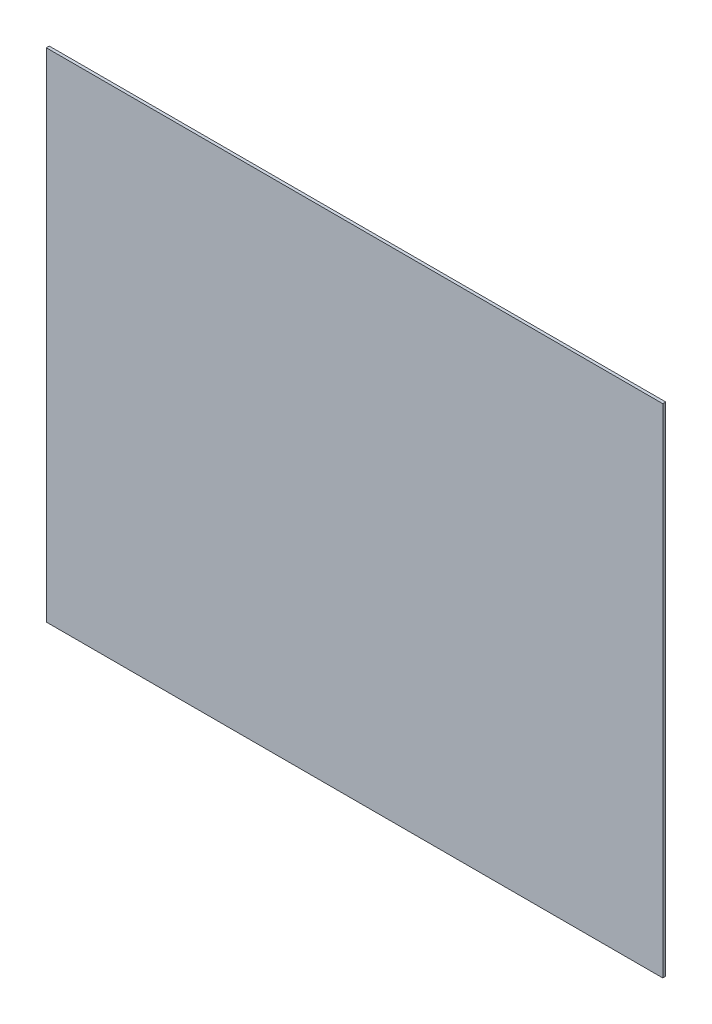
SolidWorks part; units mm, degrees
ref_plane "Front Plane" through (0, 0, 0) normal (0, 0, 1) x (1, 0, 0)
ref_plane "Top Plane" through (0, 0, 0) normal (0, 1, 0) x (1, 0, 0)
ref_plane "Right Plane" through (0, 0, 0) normal (1, 0, 0) x (0, 0, -1)
sketch "Sketch1" plane through (0, 0, 0) normal (0, 0, 1) x (1, 0, 0)
  line L1 (-581.6, -469.2) -> (581.6, -469.2)
  line L2 (-581.6, -469.2) -> (-581.6, 469.2)
  line L3 (-581.6, 469.2) -> (581.6, 469.2)
  line L4 (581.6, -469.2) -> (581.6, 469.2)
  line L5 (-581.6, -469.2) -> (581.6, 469.2) construction
  line L6 (-581.6, 469.2) -> (581.6, -469.2) construction
  line L7 (-581.6, -457.2) -> (-581.6, 457.2) construction
  line L8 (-609.6, 469.2) -> (609.6, 469.2) construction
  point P0 (0, 0)
extrude "Boss-Extrude1" add sketch "Sketch1" along normal mid plane 5.588
